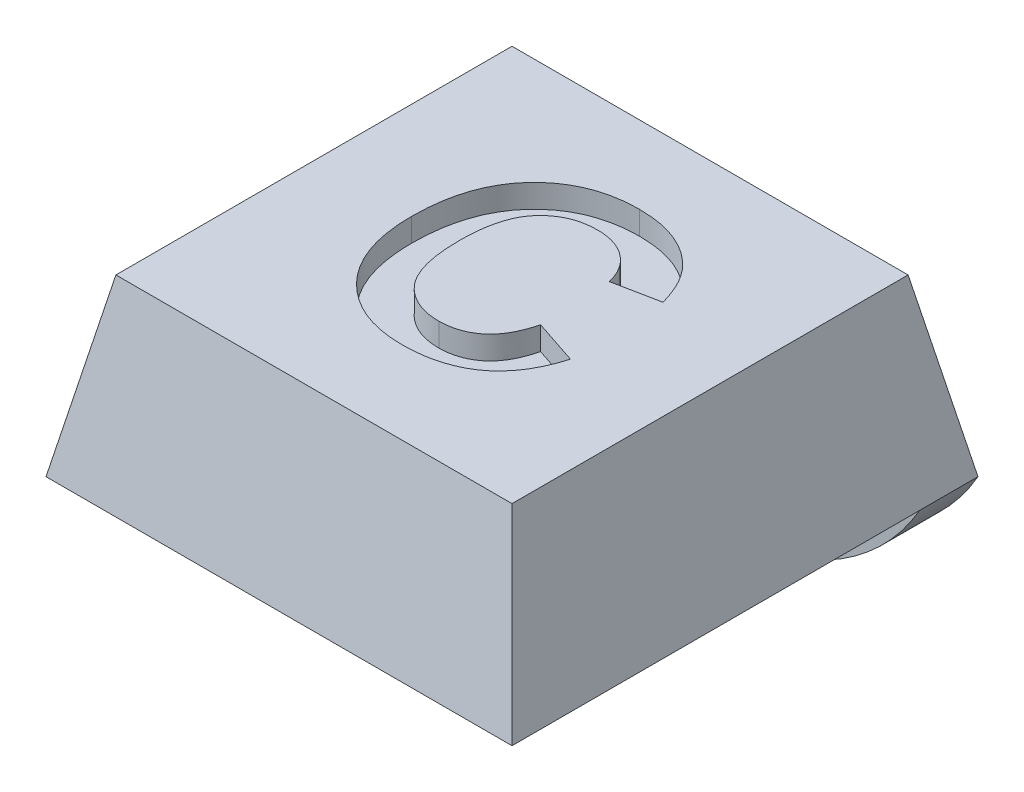
SolidWorks part; units mm, degrees
ref_plane "Front Plane" through (0, 0, 0) normal (0, 0, 1) x (1, 0, 0)
ref_plane "Top Plane" through (0, 0, 0) normal (0, 1, 0) x (1, 0, 0)
ref_plane "Right Plane" through (0, 0, 0) normal (1, 0, 0) x (0, 0, -1)
sketch "Sketch1" plane through (0, 0, 0) normal (0, 1, 0) x (1, 0, 0)
  line L1 (0, 0) -> (8, 0)
  line L2 (0, 0) -> (0, 8)
  line L3 (0, 8) -> (8, 8)
  line L4 (8, 0) -> (8, 8)
  dimension "D1" = 8
  dimension "D2" = 8
extrude "Boss-Extrude1" add sketch "Sketch1" along normal blind 3
sketch "Sketch2" plane through (0, 0, 0) normal (0, 0, 1) x (1, 0, 0)
  line L0 (0, 0) -> (0.6, 3)
  line L1 (0, 3) -> (8, 3) construction
  line L2 (0.6, 3) -> (0, 3)
  line L3 (0, 3) -> (0, 0)
  line L4 (8, 0) -> (7.4, 3)
  line L5 (7.4, 3) -> (8, 3)
  line L6 (8, 3) -> (8, 0)
  dimension "D1" = 0.6
  dimension "D2" = 0.6
extrude "Cut-Extrude1" cut sketch "Sketch2" against normal through all both and the other way through all
sketch "Sketch3" plane through (0, 0, 0) normal (1, 0, 0) x (0, 0, -1)
  line L0 (0, 0) -> (0.6, 3)
  line L1 (8, 3) -> (0, 3) construction
  line L2 (0.6, 3) -> (0, 3)
  line L3 (0, 3) -> (0, 0)
  line L4 (8, 3) -> (7.4, 3)
  line L5 (7.4, 3) -> (8, 0)
  line L6 (8, 3) -> (8, 0)
  dimension "D1" = 0.6
  dimension "D2" = 0.6
extrude "Cut-Extrude2" cut sketch "Sketch3" along normal blind 11
sketch "Sketch4" plane through (0, 0, 0) normal (0, -1, 0) x (1, 0, 0)
  line L0 (8, 0) -> (8, -8) construction
  line L3 (0, 0) -> (8, 0) construction
  circle A0 centre (4, -3.75) radius 1.8
  dimension "D1" = 3.6
  dimension "D2" = 4
  dimension "D3" = 3.75
extrude "Cut-Extrude3" cut sketch "Sketch4" against normal blind 0.8
sketch "Sketch5" plane through (0, 0, 0) normal (0, -1, 0) x (1, 0, 0)
  line L0 (8, 0) -> (8, -8) construction
  line L1 (0, -8) -> (8, -8)
  line L2 (0, -8) -> (0, -7)
  line L3 (0, -7) -> (8, -7)
  line L4 (8, -8) -> (8, -7)
  dimension "D1" = 1
extrude "Boss-Extrude2" add sketch "Sketch5" along normal blind 2
fillet "Fillet1" radius 4 2 edges at (8, -2, -7.5) (0, -2, -7.5)
sketch "Sketch6" plane through (0, 3, 0) normal (0, 1, 0) x (1, 0, 0)
  text T0 "C" font "Arial" height 4
extrude "Cut-Extrude4" cut sketch "Sketch6" against normal blind 0.4
